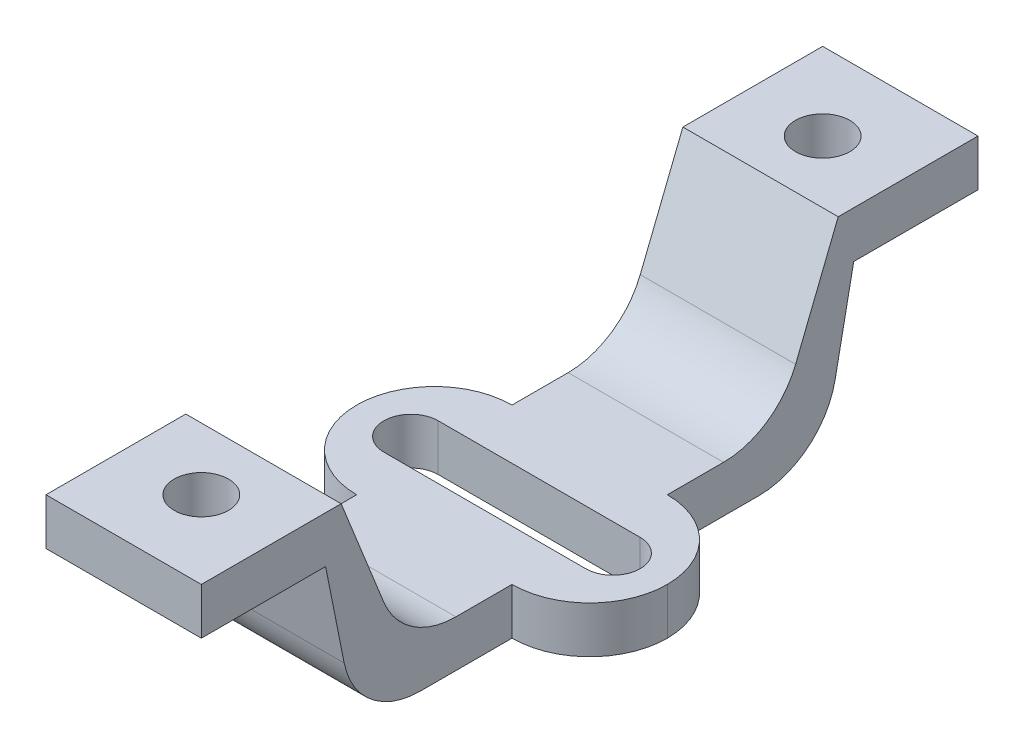
SolidWorks part; units mm, degrees
ref_plane "前视基准面" through (0, 0, 0) normal (0, 0, 1) x (1, 0, 0)
ref_plane "上视基准面" through (0, 0, 0) normal (0, 1, 0) x (1, 0, 0)
ref_plane "右视基准面" through (0, 0, 0) normal (1, 0, 0) x (0, 0, -1)
sketch "草图1" plane through (0, 0, 0) normal (0, 1, 0) x (1, 0, 0)
  line L0 (6.5, 0) -> (-6.5, 0) construction
  line L7 (10, 5) -> (-10, 5)
  line L8 (10, 5) -> (10, -5)
  line L9 (10, -5) -> (-10, -5)
  line L10 (-10, 5) -> (-10, -5)
  line L11 (10, 5) -> (-10, -5) construction
  line L12 (10, -5) -> (-10, 5) construction
  line L13 (-6.5, 1.75) -> (6.5, 1.75)
  line L14 (6.5, -1.75) -> (-6.5, -1.75)
  circle A0 centre (-6.5, 0) radius 1.75
  circle A1 centre (6.5, 0) radius 1.75
  point P0 (0, 0)
  point P6 (0, 0)
  point P14 (0, 0)
  dimension "D5" = 3.5
  dimension "D6" = 3.5
  dimension "D3" = 10
  dimension "D4" = 20
  dimension "D7" = 13
extrude "凸台-拉伸1" add sketch "草图1" along normal blind 3 contours L7 L10 L9 L8 A1 L14 A0 L13 region at (9.7764, 0, 0)
sketch "草图2" plane through (0, 0, 0) normal (1, 0, 0) x (0, 0, -1)
  line L0 (0, 3) -> (0, 13) construction
  line L1 (-25, 13) -> (25, 13) construction
  line L2 (-25, 13) -> (-25, 10)
  line L3 (-25, 10) -> (-17, 10)
  line L4 (-5, 0) -> (5, 0)
  line L5 (5, 0) -> (5, 3)
  line L6 (5, 3) -> (-5, 3)
  line L7 (-5, 3) -> (-5, 0)
  line L8 (-5, 0) -> (5, 0)
  line L9 (5, 0) -> (5, 3)
  line L10 (5, 3) -> (-5, 3)
  line L11 (-5, 3) -> (-5, 0)
  line L12 (-25, 13) -> (-17, 13)
  line L13 (-17, 13) -> (-17, 10)
  line L14 (25, 13) -> (25, 10)
  line L15 (25, 10) -> (17, 10)
  line L16 (17, 10) -> (17, 13)
  line L17 (17, 13) -> (25, 13)
  line L18 (-17, 10) -> (-15, 0)
  line L19 (-15, 0) -> (-5, 0)
  line L20 (5, 0) -> (15, 0)
  line L21 (15, 0) -> (17, 10)
  line L22 (-17, 13) -> (-16, 13)
  line L23 (-16, 13) -> (-12, 3)
  line L24 (-12, 3) -> (-5, 3)
  line L25 (5, 3) -> (12, 3)
  line L26 (12, 3) -> (16, 13)
  line L27 (16, 13) -> (17, 13)
  point P10 (0, 13)
  dimension "D2" = 10
  dimension "D3" = 50
  dimension "D4" = 8
  dimension "D5" = 8
  dimension "D6" = 3
  dimension "D7" = 3
  dimension "D8" = 1
  dimension "D9" = 1
  dimension "D10" = 10
  dimension "D11" = 10
  dimension "D12" = 7
  dimension "D13" = 7
  dimension "D1" = 0
extrude "凸台-拉伸2" add sketch "草图2" along normal mid plane 10 contours L13 L12 L2 L3 | L24 L23 L22 L13 L18 L19 L11 | L27 L26 L25 L9 L20 L21 L16 | L17 L16 L15 L14 region at (0, 11.5, 21) region at (0, 12.8231, 16.5) region at (0, 1.5, -5.1769) region at (0, 11.5, -21)
sketch "草图3" plane through (0, 13, 0) normal (0, 1, 0) x (1, 0, 0)
  line L0 (0, -20) -> (0, 20) construction
  circle A0 centre (0, 20) radius 1.75
  circle A1 centre (0, -20) radius 1.75
  point P8 (0, 0)
  dimension "D1" = 3.5
  dimension "D2" = 3.5
  dimension "D3" = 40
extrude "切除-拉伸1" cut sketch "草图3" against normal blind 10
fillet "圆角1" radius 5 4 edges at (0, 0, -15) (0, 3, -12) (0, 3, 12) (0, 0, 15)
fillet "圆角2" radius 5 4 edges at (-10, 1.5, 5) (-10, 1.5, -5) (10, 1.5, -5) (10, 1.5, 5)
